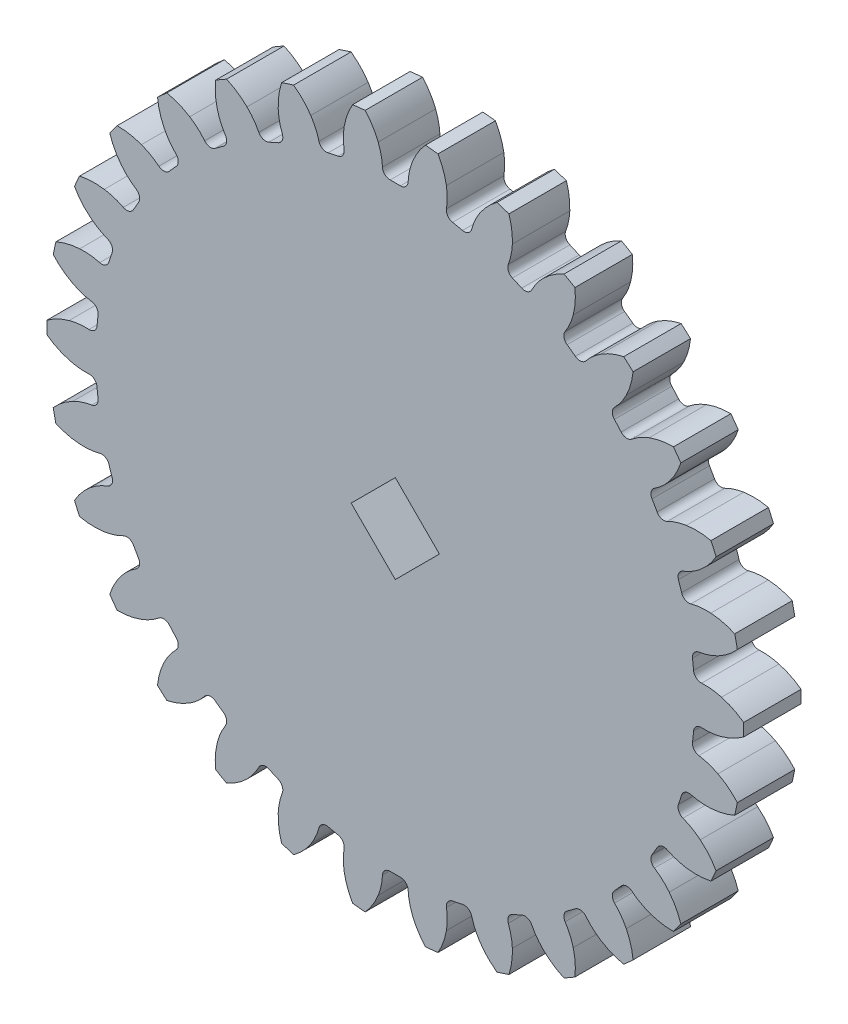
SolidWorks part; units mm, degrees
ref_plane "Front" through (0, 0, 0) normal (0, 0, 1) x (1, 0, 0)
ref_plane "Top" through (0, 0, 0) normal (0, 1, 0) x (1, 0, 0)
ref_plane "Right" through (0, 0, 0) normal (1, 0, 0) x (0, 0, -1)
sketch "Sketch1" plane through (0, 0, 0) normal (0, 0, 1) x (1, 0, 0)
  line L0 (0, 0) -> (33.2316, 0) construction
  line L1 (33.2316, 0) -> (35.447, 0) construction
  circle A0 centre (0, 0) radius 33.2316 construction
  circle A1 centre (0, 0) radius 35.447
  dimension "pitch_diameter" = 66.4632
  dimension "addendum" = 2.2154
extrude "GEAR_BASE" add sketch "Sketch1" along normal mid plane 5.842
sketch "Sketch2" plane through (0, 0, 2.921) normal (0, 0, 1) x (1, 0, 0)
  line L0 (0, 0) -> (30.4623, 0) construction
  line L1 (30.4623, 0) -> (33.2316, 0) construction
  line L2 (0, 0) -> (-35.447, 0) construction
  line L3 (0, 0) -> (-34.6724, -7.3699) construction
  line L4 (-34.7999, -6.7423) -> (-32.8226, -5.1976) construction
  line L5 (-32.8226, -5.1976) -> (-30.1529, -4.3302) construction
  line L6 (-35.4412, -0.6404) -> (-33.186, -1.7402) construction
  line L7 (-33.186, -1.7402) -> (-30.3943, -2.0336) construction
  line L8 (-32.4608, -6.8998) -> (-32.8226, -5.1976) construction
  line L9 (-33.186, -1.7402) -> (-33.186, 0) construction
  line L12 (0, 0) -> (-33.186, -1.7402) construction
  line L13 (0, 0) -> (-32.8226, -5.1976) construction
  line L14 (-32.8226, -5.1976) -> (-30.8934, -17.3808) construction
  line L15 (-33.186, -1.7402) -> (-33.8319, 10.5779) construction
  line L16 (-32.8226, -5.1976) -> (-33.186, -1.7402) construction
  line L17 (-30.2954, -3.1842) -> (-30.3943, -2.0336) construction
  line L18 (-30.2954, -3.1842) -> (-30.1529, -4.3302) construction
  circle A0 centre (0, 0) radius 33.2316 construction
  circle A1 centre (0, 0) radius 30.4623 construction
  circle A2 centre (0, 0) radius 35.447 construction
  arc A3 (-34.7999, -6.7423) -> (-35.4412, -0.6404) centre (0, 0) cw
  arc A4 (-30.1529, -4.3302) -> (-30.3943, -2.0336) centre (0, 0) cw construction
  arc A6 (-34.7999, -6.7423) -> (-32.8226, -5.1976) centre (-29.596, -11.3655) cw
  arc A7 (-35.4412, -0.6404) -> (-33.186, -1.7402) centre (-31.3123, 4.9638) ccw
  arc A8 (-32.8226, -5.1976) -> (-30.8863, -4.5583) centre (-29.912, -10.7616) cw
  arc A9 (-33.186, -1.7402) -> (-31.1591, -1.963) centre (-31.4958, 4.3073) ccw
  arc A10 (-30.8863, -4.5583) -> (-30.237, -3.6981) centre (-31.0066, -3.7923) ccw
  arc A11 (-31.1591, -1.963) -> (-30.3451, -2.6693) centre (-31.1175, -2.7372) cw
  arc A12 (-30.237, -3.6981) -> (-30.3451, -2.6693) centre (0, 0) cw
  dimension "base_fillet" = 0.7754
  dimension "D12" = 6.9609
  dimension "deddendum" = 2.7693
  dimension "D3" = 12
  dimension "D4" = 1.7402
  dimension "D5" = 1.7402
  dimension "D11" = 3.4764
  dimension "Pressure_Angle" = 20
  dimension "D14" = 9
  dimension "D15" = 9
extrude "GEAR_CUT" cut sketch "Sketch2" against normal through all
ref_axis "GEAR_AXIS" through (0, 0, 50) along (0, 0, -1)
pattern_circular "GEAR_TEETH" count 30 over 360 about axis through (0, 0, 50) along (0, 0, -1) of "GEAR_CUT"
sketch "Sketch9" plane through (0, 0, -2.921) normal (0, 0, -1) x (-1, 0, 0)
  line L0 (0, -4.4901) -> (-4.4901, 0)
  line L1 (-4.4901, 0) -> (0, 4.4901)
  line L2 (0, 4.4901) -> (4.4901, 0)
  line L3 (4.4901, 0) -> (0, -4.4901)
  circle A0 centre (0, 0) radius 4.4901
  dimension "D1" = 8.9803
extrude "Cut-Extrude2" cut sketch "Sketch9" against normal through all contours L3 L2 L1 L0 region at (0, 0, -2.921)
equation "\"N_teeth\"= 30"
equation "\"pitch_diameter\"= 2.61666"
equation "\"Pd\"=\"N_teeth\"/\"pitch_diameter\""
equation "\"addendum\"=1.000/\"Pd\""
equation "\"face_width\"=0.23"
equation "\"deddendum\"=1.250/\"Pd\""
equation "\"D3@Sketch2\" = 360/\"N_teeth\""
equation "\"tooth_thickness\"=1.571/\"Pd\""
equation "\"D4@Sketch2\" = \"tooth_thickness\"/2"
equation "\"D5@Sketch2\" = \"tooth_thickness\"/2"
equation "\"Pressure_Angle\"=20.000000"
equation "\"base_fillet\"=0.35/\"Pd\""
equation "\"D12@Sketch2\" = 2*\"tooth_thickness\""
equation "\"hub_diameter\"=1.57"
equation "\"bore\"=6.35"
equation "\"hub_projection\"=0.250000"
equation "\"sss_diam\"=0.062500"
